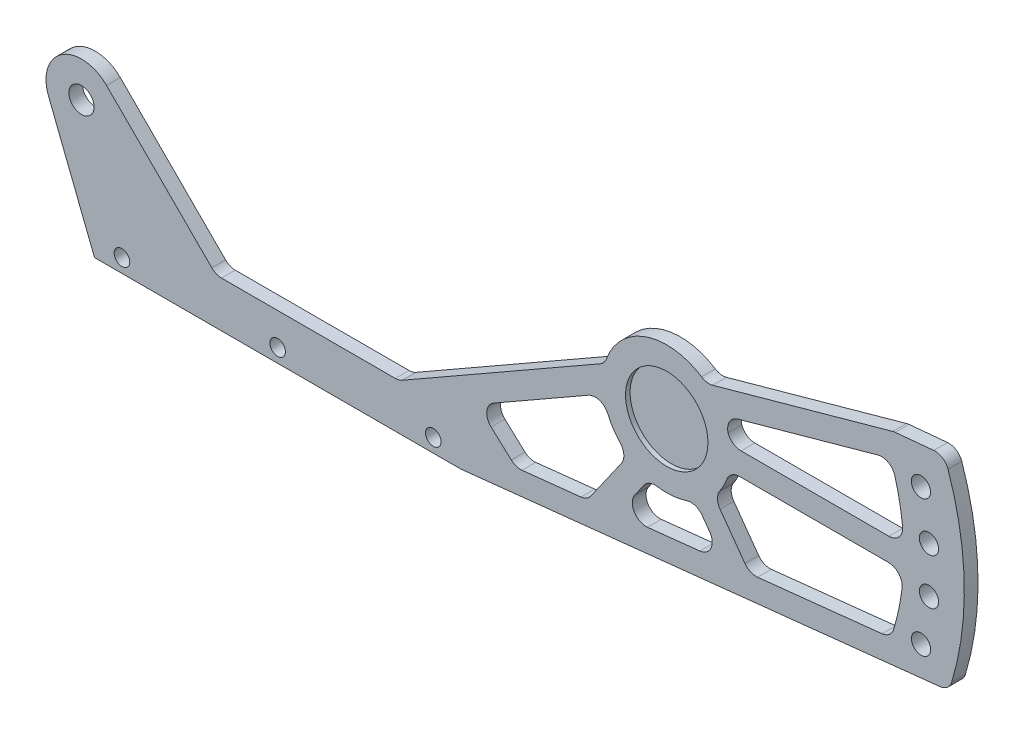
SolidWorks part; units mm, degrees
ref_plane "Спереди" through (0, 0, 0) normal (0, 0, 1) x (1, 0, 0)
ref_plane "Сверху" through (0, 0, 0) normal (0, 1, 0) x (1, 0, 0)
ref_plane "Справа" through (0, 0, 0) normal (1, 0, 0) x (0, 0, -1)
sketch "Эскиз1" plane through (0, 0, 0) normal (0, 0, 1) x (1, 0, 0)
  line L0 (0, 0) -> (80, 0)
  line L1 (80, 0) -> (186.6474, 11.3941)
  line L3 (185.6418, 55.4002) -> (29.8179, 40.9591)
  line L4 (29.8179, 40.9591) -> (0, 40.9591)
  line L5 (0, 40.9591) -> (0, 0)
  arc A1 (186.6474, 11.3941) -> (185.6418, 55.4002) centre (125, 32) ccw
  point P13 (0, 0)
  dimension "D3" = 130
  dimension "D1" = 80
extrude "Бобышка-Вытянуть1" add sketch "Эскиз1" along normal blind 3
sketch "Эскиз2" plane through (0, 0, 3) normal (0, 0, 1) x (1, 0, 0)
  line L0 (-2.7509, 3) -> (78.5336, 3) construction
  line L1 (0, 0) -> (80, 0) construction
  line L2 (6, 6.1653) -> (6, -1.4851) construction
  line L4 (74, 6.1653) -> (74, -1.4851) construction
  line L5 (0, 40.9591) -> (0, 0) construction
  line L6 (40, 0) -> (40, 7.0416) construction
  dimension "D1" = 3
  dimension "D2" = 6
  dimension "D4" = 6
hole_wizard "Отверстие с зазором M31" positions "Эскиз4" profile "Эскиз3" hole size "M3" standard "Ansi Metric" end condition through all
sketch "Эскиз4" plane through (0, 0, 3) normal (0, 0, 1) x (1, 0, 0)
  line L0 (-2.7509, 3) -> (78.5336, 3) construction
  line L1 (6, 6.1653) -> (6, -1.4851) construction
  line L3 (74, 6.1653) -> (74, -1.4851) construction
  line L4 (40, 0) -> (40, 7.0416) construction
  point P0 (6, 3)
  point P6 (40, 3)
  point P10 (74, 3)
sketch "Эскиз3" plane through (6, 3, 3) normal (1, 0, 0) x (0, -1, 0)
  line L0 (0, 0) -> (0, 3)
  line L1 (0, 3) -> (1.7, 3)
  line L2 (1.7, 3) -> (1.7, 0)
  line L5 (1.7, 0) -> (0, 0)
  line L11 (0, -6.35) -> (0, 107.95) construction
  dimension "Диаметр сквозного отверстия" = 3.4
  dimension "Глубина сквозного отверстия" = 3
sketch "Эскиз5" plane through (0, 0, 3) normal (0, 0, 1) x (1, 0, 0)
  line L0 (-10.0586, 25.5565) -> (0, 0)
  line L1 (0, 0) -> (0, 21.1867)
  circle A0 centre (-2.847, 28.3948) radius 2.75
  arc A1 (0, 21.1867) -> (-10.0586, 25.5565) centre (-2.847, 28.3948) ccw
  circle A3 centre (-2.847, 28.3948) radius 7.75 construction
  point P7 (4.903, 28.3948)
  dimension "D1" = 5.5
  dimension "D2" = 5
extrude "Бобышка-Вытянуть2" add sketch "Эскиз5" against normal up to surface (3 mm away) up to face at (7.7, 3, 0)
sketch "Эскиз6" plane through (0, 0, 3) normal (0, 0, 1) x (1, 0, 0)
  line L0 (-10.4862, 10) -> (81.8154, 10) construction
  line L1 (0, 0) -> (80, 0) construction
  line L2 (2.633, 33.8749) -> (26.5079, 10)
  line L3 (26.5079, 10) -> (66.5079, 10)
  line L4 (66.5079, 10) -> (104.3768, 47.8689)
  line L5 (185.6418, 55.4002) -> (29.8179, 40.9591) construction
  line L6 (104.3768, 47.8689) -> (29.8179, 40.9591)
  line L7 (29.8179, 40.9591) -> (0, 40.9591)
  line L8 (0, 40.9591) -> (0, 35.6029)
  line L9 (0.7482, 30) -> (105.8715, 30) construction
  arc A0 (0, 35.6029) -> (2.633, 33.8749) centre (-2.847, 28.3948) cw
  dimension "D2" = 20
  dimension "D4" = 45
  dimension "D3" = 45
  dimension "D1" = 10
  dimension "D5" = 40
extrude "Вырез-Вытянуть1" cut sketch "Эскиз6" against normal through all
sketch "Эскиз7" plane through (0, 0, 3) normal (0, 0, 1) x (1, 0, 0)
  line L0 (125, 32) -> (180.5279, 46.9298) construction
  line L1 (125, 32) -> (182.2769, 37.0606) construction
  line L2 (125, 32) -> (182.2855, 27.0377) construction
  line L3 (125, 32) -> (180.5535, 17.1656) construction
  circle A0 centre (125, 32) radius 57.5 construction
  dimension "D1" = 115
  dimension "D2" = 10
  dimension "D3" = 10
  dimension "D4" = 10
hole_wizard "Отверстие обработанное метчиком M5x0.81" positions "Эскиз9" profile "Эскиз8" tap size "M5x0.8" standard "Ansi Metric" end condition through all
sketch "Эскиз9" plane through (0, 0, 3) normal (0, 0, 1) x (1, 0, 0)
  point P0 (180.5279, 46.9298)
  point P3 (182.2769, 37.0606)
  point P6 (182.2855, 27.0377)
  point P9 (180.5535, 17.1656)
sketch "Эскиз8" plane through (180.5279, 46.9298, 3) normal (1, 0, 0) x (0, -1, 0)
  line L0 (0, 0) -> (0, 3)
  line L1 (0, 3) -> (2.1, 3)
  line L2 (2.1, 3) -> (2.1, 0)
  line L5 (2.1, 0) -> (0, 0)
  line L11 (0, -6.35) -> (0, 107.95) construction
  dimension "Диаметр проходного сверла" = 4.2
  dimension "Глубина проходного сверла" = 3
cosmetic thread "Отверстие резьбы1"
cosmetic thread "Отверстие резьбы2"
cosmetic thread "Отверстие резьбы3"
cosmetic thread "Отверстие резьбы4"
sketch "Эскиз10" plane through (0, 0, 3) normal (0, 0, 1) x (1, 0, 0)
  line L0 (66.5079, 10) -> (111.5092, 35.7414)
  line L1 (133.6695, 42.9927) -> (174.6526, 54.3818)
  line L2 (185.6418, 55.4002) -> (104.3768, 47.8689) construction
  line L3 (66.5079, 10) -> (104.3768, 47.8689)
  line L4 (104.3768, 47.8689) -> (174.6526, 54.3818)
  arc A0 (133.6695, 42.9927) -> (111.5092, 35.7414) centre (125, 32) ccw
  dimension "D1" = 28
extrude "Вырез-Вытянуть2" cut sketch "Эскиз10" against normal through all
sketch "Эскиз11" plane through (0, 0, 3) normal (0, 0, 1) x (1, 0, 0)
  line L0 (92.0344, 6.3142) -> (107.6302, 7.9804)
  line L1 (173.9308, 48.9917) -> (137.2401, 38.7955)
  line L2 (83.6238, 14.0303) -> (111.1755, 29.7903)
  line L3 (133.6695, 42.9927) -> (174.6526, 54.3818) construction
  line L4 (80, 0) -> (186.6474, 11.3941) construction
  line L5 (66.5079, 10) -> (111.5092, 35.7414) construction
  line L6 (83.6238, 14.0303) -> (92.0344, 6.3142)
  line L7 (116.6083, 20.7938) -> (107.6302, 7.9804)
  line L8 (121.1368, 18.5436) -> (114.2295, 8.6855)
  line L9 (125, 32) -> (104.4053, 2.6074) construction
  line L10 (131.3501, 19.523) -> (137.3788, 11.1587)
  line L11 (125, 32) -> (150.9131, -3.9523) construction
  line L12 (143.1015, 11.7701) -> (173.9508, 15.0661)
  line L13 (135.3307, 22.5514) -> (143.1015, 11.7701)
  line L14 (138.8492, 34.0496) -> (176.7565, 34.0496)
  line L15 (138.6856, 29.0496) -> (176.713, 29.0496)
  line L16 (125, 32) -> (176.7971, 32) construction
  line L17 (114.2295, 8.6855) -> (137.3788, 11.1587)
  arc A0 (138.8492, 34.0496) -> (137.2401, 38.7955) centre (125, 32) ccw
  arc A1 (133.6695, 42.9927) -> (111.5092, 35.7414) centre (125, 32) ccw construction
  arc A2 (173.9508, 15.0661) -> (176.713, 29.0496) centre (125, 32) ccw
  arc A3 (135.3307, 22.5514) -> (138.6856, 29.0496) centre (125, 32) ccw
  arc A4 (121.1368, 18.5436) -> (131.3501, 19.523) centre (125, 32) ccw
  arc A5 (111.1755, 29.7903) -> (116.6083, 20.7938) centre (125, 32) ccw
  arc A6 (176.7565, 34.0496) -> (173.9308, 48.9917) centre (125, 32) ccw
  dimension "D1" = 5
  dimension "D2" = 5
  dimension "D3" = 5
  dimension "D4" = 5
  dimension "D5" = 5
  dimension "D6" = 5
extrude "Вырез-Вытянуть3" cut sketch "Эскиз11" against normal through all
fillet "Скругление1" radius 3 25 edges at (138.8492, 34.0496, 1.5) (173.9308, 48.9917, 1.5) (176.713, 29.0496, 1.5) (143.1015, 11.7701, 1.5) (83.6238, 14.0303, 1.5) (92.0344, 6.3142, 1.5) (114.2295, 8.6855, 1.5) (131.3501, 19.523, 1.5) (121.1368, 18.5436, 1.5) (137.2401, 38.7955, 1.5) (135.3307, 22.5514, 1.5) (138.6856, 29.0496, 1.5) (173.9508, 15.0661, 1.5) (176.7565, 34.0496, 1.5) (107.6302, 7.9804, 1.5) (137.3788, 11.1587, 1.5) (116.6083, 20.7938, 1.5) (111.1755, 29.7903, 1.5) (66.5079, 10, 1.5) (26.5079, 10, 1.5) (186.6474, 11.3941, 1.5) (111.5092, 35.7414, 1.5) (133.6695, 42.9927, 1.5) (185.6418, 55.4002, 1.5) (174.6526, 54.3818, 1.5)
sketch "Эскиз12" plane through (0, 0, 3) normal (0, 0, 1) x (1, 0, 0)
  circle A0 centre (125, 32) radius 9
  dimension "D1" = 18
extrude "Вырез-Вытянуть4" cut sketch "Эскиз12" against normal blind 1
equation "\"D3@Эскиз7\"=\"D2@Эскиз7\""
equation "\"D4@Эскиз7\"=\"D2@Эскиз7\""
